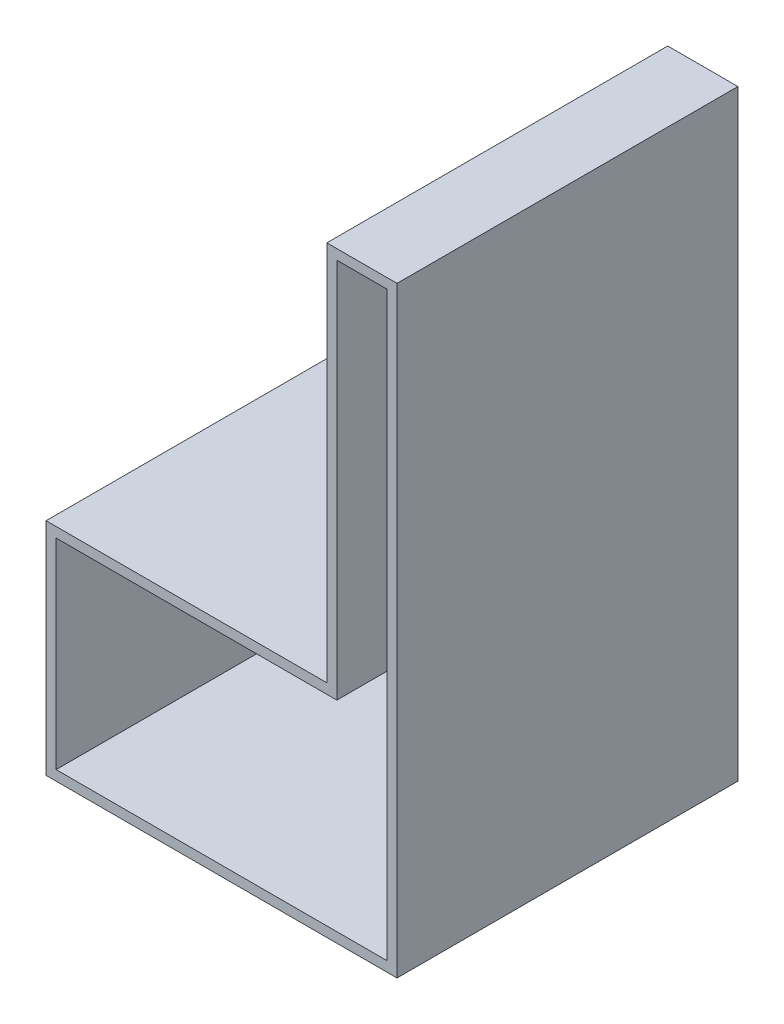
SolidWorks part; units mm, degrees
ref_plane "正面" through (0, 0, 0) normal (0, 0, 1) x (1, 0, 0)
ref_plane "平面" through (0, 0, 0) normal (0, 1, 0) x (1, 0, 0)
ref_plane "右側面" through (0, 0, 0) normal (1, 0, 0) x (0, 0, -1)
sketch "ｽｹｯﾁ2" plane through (0, 0, 0) normal (0, 0, 1) x (1, 0, 0)
  line L0 (0, 0) -> (0, 190)
  line L1 (0, 190) -> (35, 190)
  line L2 (35, 190) -> (35, -110)
  line L3 (35, -110) -> (-140, -110)
  line L4 (-140, -110) -> (-140, 0)
  line L5 (-140, 0) -> (0, 0)
  dimension "D1" = 110
  dimension "D2" = 175
  dimension "D3" = 35
  dimension "D4" = 300
extrude "ﾎﾞｽ - 押し出し1" add sketch "ｽｹｯﾁ2" along normal blind 170
shell "ｼｪﾙ1" thickness 5 removed face at (-35, 26.6667, 170)
